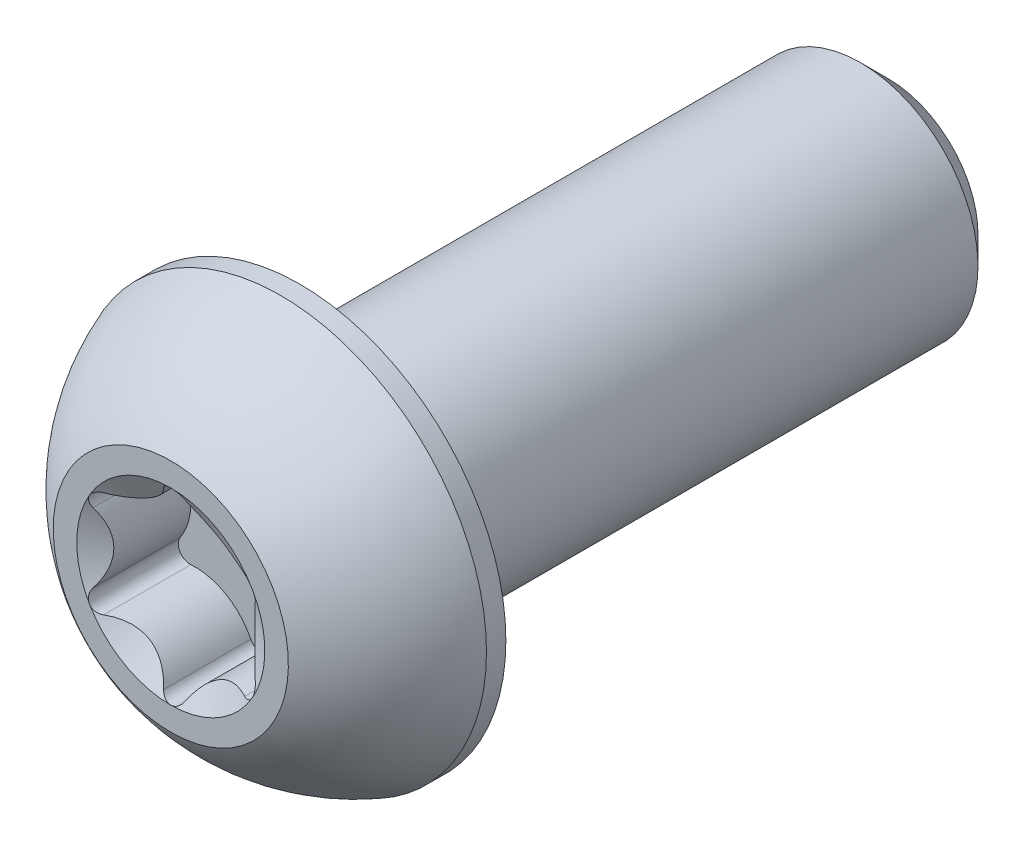
SolidWorks part; units mm, degrees
ref_plane "Front" through (0, 0, 0) normal (0, 0, 1) x (1, 0, 0)
ref_plane "Top" through (0, 0, 0) normal (0, 1, 0) x (1, 0, 0)
ref_plane "Right" through (0, 0, 0) normal (1, 0, 0) x (0, 0, -1)
sketch "Sketch1" plane through (0, 0, 0) normal (1, 0, 0) x (0, 0, -1)
  line L2 (4.4, 4) -> (24.4, 4)
  line L3 (24.4, 4) -> (24.4, 0)
  line L4 (24.4, 0) -> (4.4, 0)
  line L6 (3.74, 7) -> (4.4, 7) construction
  line L7 (24.4, 4) -> (24.4, -4) construction
  line L8 (0, 0) -> (4.4, 0) construction
  line L9 (4.4, 7) -> (4.4, -7) construction
  line L11 (4.4, 4) -> (4.4, 0)
  line L14 (0, 0) -> (0, 4) construction
  arc A3 (0, 4) -> (3.74, 7) centre (6.2818, 0) cw construction
  dimension "D1" = 0.66
revolve "Revolve1" add sketch "Sketch1" angle 360 mid plane about L4
sketch "Sketch3" plane through (0, 0, -24.4) normal (0, 0, -1) x (-1, 0, 0)
  circle A0 centre (0, 0) radius 4
curve "Helix/Spiral1" pitch 1.25 height 21.25 turns 17
sketch "Sketch2" plane through (0, 0, 0) normal (1, 0, 0) x (0, 0, -1)
  line L0 (24.4, 4) -> (25.4937, 4)
  line L1 (25.4937, 4) -> (25.025, 3.1881)
  line L2 (25.025, 3.1881) -> (24.8687, 3.1881)
  line L3 (24.8687, 3.1881) -> (24.4, 4)
  line L4 (24.6344, 3.5941) -> (25.2594, 3.5941) construction
  dimension "D1" = 60
  dimension "D2" = 0.1562
  dimension "D3" = 0.625
chamfer "Chamfer1" distance 0.9375 angle 45 1 edges at (0, 4, -24.4)
sweep "Cut-Sweep1" [suppressed] cut profiles "Sketch2" path "Helix/Spiral1"
sketch "Sketch7" plane through (0, 0, 0) normal (1, 0, 0) x (0, 0, -1)
  line L0 (0, 0) -> (0, 4) construction
  line L6 (3.74, 7) -> (4.4, 7) construction
  line L8 (0, 0) -> (4.4, 0) construction
  line L11 (4.4, 7) -> (4.4, -7) construction
  line L12 (3.74, 7) -> (4.4, 7)
  line L13 (0, 0) -> (4.4, 0)
  line L15 (4.4, 7) -> (4.4, 0)
  line L16 (0, 4) -> (0, 0)
  arc A2 (3.74, 7) -> (0, 4) centre (6.2818, 0) ccw construction
  arc A3 (3.74, 7) -> (0, 4) centre (6.2818, 0) ccw
revolve "Revolve2" add sketch "Sketch7" angle 360 mid plane about L13
sketch "Sketch11" plane through (0, 0, 0) normal (0, 0, 1) x (1, 0, 0)
  line L0 (0, 0) -> (-2.7713, 1.6)
  line L1 (0, 0) -> (-2.7713, -1.6)
  line L2 (0, 3.2) -> (0, 2.8) construction
  line L3 (0, 2.8) -> (0, 2.4) construction
  line L4 (7.7, 0) -> (-7.7, 0) construction
  circle A0 centre (0, 0) radius 2.4 construction
  circle A1 centre (0, 0) radius 2.8 construction
  circle A2 centre (0, 0) radius 3.2 construction
  arc A3 (-2.7574, 1.1777) -> (-2.7574, -1.1777) centre (-4.519, 0) cw
  arc A4 (-2.7574, 1.1777) -> (-2.7713, 1.6) centre (-2.4249, 1.4) cw
  arc A5 (-2.7574, -1.1777) -> (-2.7713, -1.6) centre (-2.4249, -1.4) ccw
  dimension "D1" = 4.8
  dimension "D2" = 6.4
  dimension "D3" = 30
extrude "Cut-Extrude4" cut sketch "Sketch11" against normal blind 3.08
pattern_circular "CirPattern1" count 6 over 360 of "Cut-Extrude4"
sketch "Sketch6" plane through (0, 0, 0) normal (0, 0, 1) x (1, 0, 0)
  circle A0 centre (0, 0) radius 3.2 construction
  circle A1 centre (0, 0) radius 3.2
extrude "Cut-Extrude3" cut sketch "Sketch6" against normal blind 3.08 draft 60
sketch "Sketch9" [suppressed] plane through (0, 0, -5.5) normal (0, 0, 1) x (1, 0, 0)
  circle A2 centre (0, 0) radius 5
extrude "Boss-Extrude2" [suppressed] add sketch "Sketch9" against normal offset from surface (13 mm away) 32
sketch "Sketch10" plane through (0, 0, 0) normal (1, 0, 0) x (0, 0, -1)
  line L0 (24.4, 4) -> (24.4, -4) construction
  point P0 (22.525, -4)
  dimension "D1" = 1.875
equation "\"D3@Helix/Spiral1\" = \"Lg@Sketch1\" + \"D4@Helix/Spiral1\""
equation "\"D2@Sketch2\" = \"D4@Helix/Spiral1\" * .125"
equation "\"D3@Sketch2\" = \"D4@Helix/Spiral1\" * .5"
equation "\"D1@Chamfer1\" = \"D4@Helix/Spiral1\" * .75"
equation "\"D1@Sketch1\" = \"Head Ht@Sketch1\" * .15"
equation "\"D1@Sketch10\" = \"D4@Helix/Spiral1\" * 1.5"
equation "\"D2@Sketch11\" = \"Dia@Sketch1\" * .8"
equation "\"D1@Sketch11\" = \"D2@Sketch11\" * .75"
equation "\"D1@Cut-Extrude4\" = \"Head Ht@Sketch1\" * .7"
equation "\"D1@Cut-Extrude3\" = \"D1@Cut-Extrude4\""
